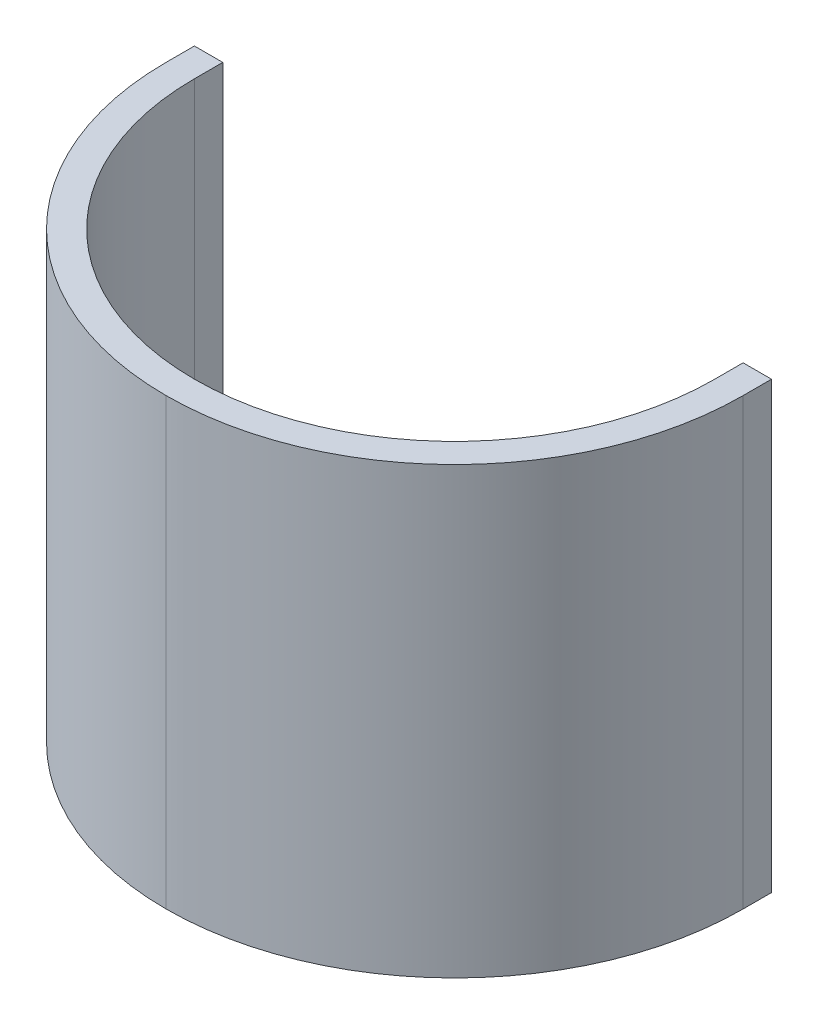
SolidWorks part; units mm, degrees
ref_plane "정면" through (0, 0, 0) normal (0, 0, 1) x (1, 0, 0)
ref_plane "윗면" through (0, 0, 0) normal (0, 1, 0) x (1, 0, 0)
ref_plane "우측면" through (0, 0, 0) normal (1, 0, 0) x (0, 0, -1)
sketch "스케치1" plane through (0, 0, 0) normal (0, 1, 0) x (1, 0, 0)
  line L1 (-30.5, -16.75) -> (30.5, -16.75)
  line L2 (-30.5, -16.75) -> (-30.5, 16.75)
  line L3 (-30.5, 16.75) -> (30.5, 16.75)
  line L4 (30.5, -16.75) -> (30.5, 16.75)
  line L5 (-30.5, -16.75) -> (30.5, 16.75) construction
  line L6 (-30.5, 16.75) -> (30.5, -16.75) construction
  point P0 (0, 0)
  dimension "D1" = 61
  dimension "D2" = 33.5
extrude "보스-돌출1" add sketch "스케치1" along normal blind 50
sketch "스케치2" plane through (0, 0, -16.75) normal (0, 0, -1) x (-1, 0, 0)
  line L0 (0, 0) -> (0, 50) construction
  line L1 (-30.5, 50) -> (30.5, 50) construction
  line L2 (-30.5, 25) -> (30.5, 25) construction
  line L3 (-30.5, 50) -> (-30.5, 0) construction
  line L4 (30.5, 50) -> (30.5, 0) construction
  line L5 (-30.5, 0) -> (30.5, 0) construction
  line L6 (-27.5, 3) -> (27.5, 3)
  line L7 (-27.5, 3) -> (-27.5, 47)
  line L8 (-27.5, 47) -> (27.5, 47)
  line L9 (27.5, 3) -> (27.5, 47)
  line L10 (-27.5, 3) -> (27.5, 47) construction
  line L11 (-27.5, 47) -> (27.5, 3) construction
  point P11 (0, 25)
  dimension "D1" = 3
  dimension "D2" = 3
extrude "컷-돌출1" cut sketch "스케치2" against normal blind 30.5
fillet "필렛3" radius 27.5 2 edges at (-27.5, 25, 13.75) (27.5, 25, 13.75)
fillet "필렛4" radius 30.5 2 edges at (-30.5, 25, 16.75) (30.5, 25, 16.75)
sketch "스케치3" plane through (0, 0, 0) normal (0, -1, 0) x (1, 0, 0)
  line L1 (-30.5, -13.75) -> (30.5, -13.75) construction
  circle A0 centre (0, -13.75) radius 23.5
  arc A1 (30.5, -13.75) -> (0, 16.75) centre (0, -13.75) ccw construction
  dimension "D1" = 7
extrude "컷-돌출2" cut sketch "스케치3" against normal blind 30.5
sketch "스케치5" plane through (0, 47, 0) normal (0, -1, 0) x (1, 0, 0)
  line L0 (-23.5, -13.75) -> (23.5, -13.75) construction
  arc A0 (23.3077, -16.75) -> (-23.3077, -16.75) centre (0, -13.75) ccw construction
  circle A1 centre (0, -13.75) radius 16
extrude "컷-돌출4" cut sketch "스케치5" against normal blind 30.5
fillet "필렛5" radius 4 2 edges at (15.7162, 48.5, -16.75) (-15.7162, 48.5, -16.75)
fillet "필렛6" radius 2 2 edges at (23.3077, 1.5, -16.75) (-23.3077, 1.5, -16.75)
sketch "스케치6" plane through (0, 0, -16.75) normal (0, 0, -1) x (-1, 0, 0)
  line L0 (30.5, 50) -> (30.5, 0) construction
  line L1 (-30.5, 50) -> (30.5, 50)
  line L2 (-30.5, 50) -> (-30.5, 47)
  line L3 (-30.5, 47) -> (30.5, 47)
  line L4 (30.5, 50) -> (30.5, 47)
  dimension "D1" = 3
extrude "컷-돌출5" cut sketch "스케치6" against normal blind 400
